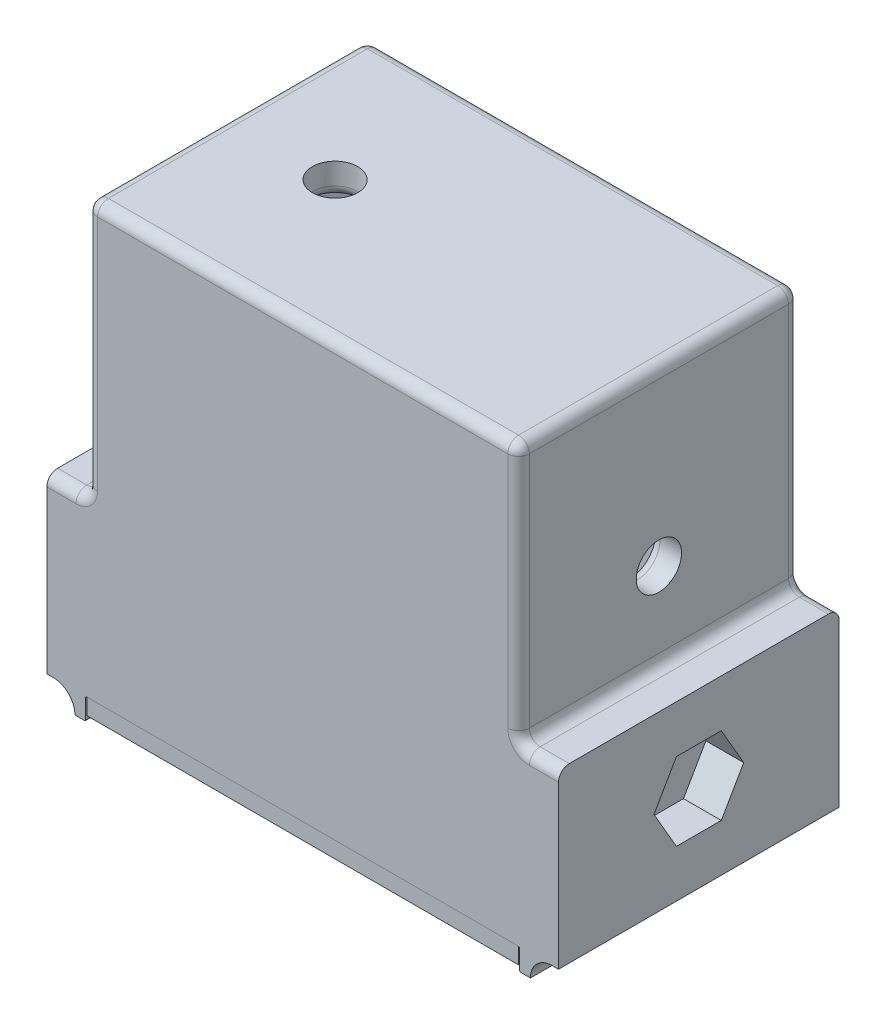
SolidWorks part; units mm, degrees
other "Gasket (DISABLE WHEN 3D PRINTING)" parameters "D1"=40, "D2"=18.2927
ref_plane "Front Plane" through (0, 0, 0) normal (0, 0, 1) x (1, 0, 0)
ref_plane "Top Plane" through (0, 0, 0) normal (0, 1, 0) x (1, 0, 0)
ref_plane "Right Plane" through (0, 0, 0) normal (1, 0, 0) x (0, 0, -1)
sketch "Sketch1" plane through (0, 0, 0) normal (0, 1, 0) x (1, 0, 0)
  line L1 (-20, 13) -> (20, 13)
  line L2 (-20, 13) -> (-20, -13)
  line L3 (-20, -13) -> (20, -13)
  line L4 (20, 13) -> (20, -13)
  line L5 (-20, 13) -> (20, -13) construction
  line L6 (-20, -13) -> (20, 13) construction
  point P4 (0, 0)
  dimension "D1" = 40
  dimension "D2" = 26
extrude "Body" add sketch "Sketch1" along normal blind 40
sketch "Sketch2" plane through (0, 0, 0) normal (0, 1, 0) x (1, 0, 0)
  line L0 (0, -24.6326) -> (0, 25.7324) construction
  line L1 (-20, -13) -> (-23.7, -13)
  line L2 (-20, -13) -> (-20, 13)
  line L3 (-20, 13) -> (-23.7, 13)
  line L4 (-23.7, -13) -> (-23.7, 13)
  line L5 (-20, -13) -> (-23.7, 13) construction
  line L6 (-20, 13) -> (-23.7, -13) construction
  line L7 (20, 13) -> (23.7, 13)
  line L8 (23.7, -13) -> (23.7, 13)
  line L9 (20, -13) -> (23.7, -13)
  line L10 (20, -13) -> (20, 13)
  point P4 (-21.85, 0)
  dimension "D1" = 3.7
extrude "Extension" add sketch "Sketch2" along normal blind 16
sketch "Nut Alignment Sketch" plane through (0, 0, 0) normal (1, 0, 0) x (0, 0, -1)
  line L0 (-13, 16) -> (13, 0) construction
  circle A0 centre (0, 8) radius 2.5 construction
  dimension "D1" = 5
sketch "Sketch5" plane through (0, 0, 0) normal (0, 1, 0) x (1, 0, 0)
  line L1 (-17, -10) -> (17, -10)
  line L2 (-17, -10) -> (-17, 10)
  line L3 (-17, 10) -> (17, 10)
  line L4 (17, -10) -> (17, 10)
  line L5 (-17, -10) -> (17, 10) construction
  line L6 (-17, 10) -> (17, -10) construction
  line L7 (-20, 13) -> (-20, -13) construction
  line L8 (-23.7, -13) -> (23.7, -13) construction
  line L9 (-20, 13) -> (-20, -13) construction
  point P4 (0, 0)
  dimension "D1" = 3
  dimension "D2" = 3
extrude "Cavity" cut sketch "Sketch5" along normal blind 37
sketch "Sketch6" plane through (0, 40, 0) normal (0, 1, 0) x (1, 0, 0)
  line L0 (0, 5.2625) -> (0, 72.0397) construction
  line L1 (-26.607, 0) -> (21.944, 0) construction
  circle A0 centre (-10, 0) radius 2.1
  dimension "D2" = 4.2
  dimension "D1" = 10
extrude "Top Hole" cut sketch "Sketch6" against normal up to next
sketch "Sketch7" plane through (20, 0, 0) normal (1, 0, 0) x (0, 0, -1)
  line L0 (-13, 28) -> (13, 28) construction
  line L1 (-13, 40) -> (-13, 16) construction
  line L2 (13, 40) -> (13, 16) construction
  line L4 (0, 41.5439) -> (0, 6.2839) construction
  circle A0 centre (0, 24) radius 2.1
  dimension "D2" = 4.2
  dimension "D1" = 4
extrude "Side Hole" cut sketch "Sketch7" against normal up to next
sketch "Sketch3" plane through (0, 0, 0) normal (0, 1, 0) x (1, 0, 0)
  line L0 (-23.7, -13) -> (23.7, -13) construction
  line L1 (-21.1, -13) -> (-20.1, -13)
  line L2 (-21.1, -13) -> (-21.1, 13)
  line L3 (-21.1, 13) -> (-20.1, 13)
  line L4 (-20.1, -13) -> (-20.1, 13)
  line L5 (-21.1, -13) -> (-20.1, 13) construction
  line L6 (-21.1, 13) -> (-20.1, -13) construction
  line L7 (23.7, 13) -> (-23.7, 13) construction
  line L8 (0, -26.2727) -> (0, 27.5208) construction
  line L9 (-23.7, 13) -> (-23.7, -13) construction
  line L10 (23.7, -13) -> (23.7, 13) construction
  line L11 (21.1, 13) -> (20.1, 13)
  line L12 (20.1, -13) -> (20.1, 13)
  line L13 (21.1, -13) -> (20.1, -13)
  line L14 (21.1, -13) -> (21.1, 13)
  point P4 (-20.6, 0)
  dimension "D1" = 1
  dimension "D2" = 20.1
  dimension "D3" = 23.7
  dimension "D4" = 23.7
extrude "Legs" add sketch "Sketch3" against normal blind 2
sketch "Sketch4" plane through (-23.7, 0, 0) normal (-1, 0, 0) x (0, 0, 1)
  line L0 (-13, 16) -> (13, 0) construction
  line L2 (2.0785, 11.6) -> (-2.0785, 11.6)
  line L3 (-2.0785, 11.6) -> (-4.1569, 8)
  line L4 (-4.1569, 8) -> (-2.0785, 4.4)
  line L5 (-2.0785, 4.4) -> (2.0785, 4.4)
  line L6 (2.0785, 4.4) -> (4.1569, 8)
  line L7 (4.1569, 8) -> (2.0785, 11.6)
  circle A0 centre (0, 8) radius 3.6 construction
  dimension "D1" = 7.2
extrude "Mount Counterbore" cut sketch "Sketch4" against normal blind 3.5
mirror "Mount Counterbore Mirror" about plane through (0, 0, 0) normal (1, 0, 0) of "Mount Counterbore"
fillet "2mm Leg Fillet" radius 2 2 edges at (21.1, 0, 0) (-21.1, 0, 0)
fillet "0.1mm Leg Fillet" radius 0.1 4 edges at (-20.1, -2, 0) (-20.1, 0, 0) (20.1, -2, 0) (20.1, 0, 0)
fillet "Outer Boundary Fillet" radius 1 14 edges at (-20, 16, 0) (-21.85, 16, -13) (-20, 28, -13) (-20, 40, 0) (0, 40, -13) (20, 40, 0) (20, 28, -13) (21.85, 16, -13) (20, 16, 0) (-21.85, 16, 13) (-20, 28, 13) (0, 40, 13) (20, 28, 13) (21.85, 16, 13)
fillet "Inner Boundary Fillet" radius 1 10 edges at (-10, 37, -2.1) (17, 24, 2.1) (17, 18.5, -10) (-17, 18.5, 10) (-17, 18.5, -10) (0, 37, -10) (-17, 37, 0) (0, 37, 10) (17, 37, 0) (17, 18.5, 10)
sketch "Sketch8" plane through (0, 0, 0) normal (0, -1, 0) x (1, 0, 0)
  line L4 (-16, -10) -> (16, -10)
  line L5 (-17, 9) -> (-17, -9)
  line L6 (16, 10) -> (-16, 10)
  line L7 (17, -9) -> (17, 9)
  line L8 (-16, -10) -> (16, -10)
  line L9 (-17, 9) -> (-17, -9)
  line L10 (16, 10) -> (-16, 10)
  line L11 (17, -9) -> (17, 9)
  line L12 (-20, -13) -> (20, -13)
  line L13 (20, -13) -> (20, 13)
  line L14 (20, 13) -> (-20, 13)
  line L15 (-20, 13) -> (-20, -13)
  line L16 (-20, -13) -> (20, -13)
  line L17 (20, -13) -> (20, 13)
  line L18 (20, 13) -> (-20, 13)
  line L19 (-20, 13) -> (-20, -13)
  arc A4 (-17, -9) -> (-16, -10) centre (-16, -9) ccw
  arc A5 (-16, 10) -> (-17, 9) centre (-16, 9) ccw
  arc A6 (17, 9) -> (16, 10) centre (16, 9) ccw
  arc A7 (16, -10) -> (17, -9) centre (16, -9) ccw
  arc A8 (-17, -9) -> (-16, -10) centre (-16, -9) ccw
  arc A9 (-16, 10) -> (-17, 9) centre (-16, 9) ccw
  arc A10 (17, 9) -> (16, 10) centre (16, 9) ccw
  arc A11 (16, -10) -> (17, -9) centre (16, -9) ccw
  dimension "D1" = 0
  dimension "D2" = 0
extrude "Boss-Extrude1" add sketch "Sketch8" along normal blind 1.5 separate body
equation "\"Height\"= 40mm"
equation "\"D1@Body\"=\"Height\""
equation "\"Length\"= 40mm"
equation "\"Width\"= 26mm"
equation "\"D2@Sketch1\"=\"Width\""
equation "\"D1@Sketch1\"=\"Length\""
equation "\"D1@Cavity\" = \"Height\" - 3mm"
